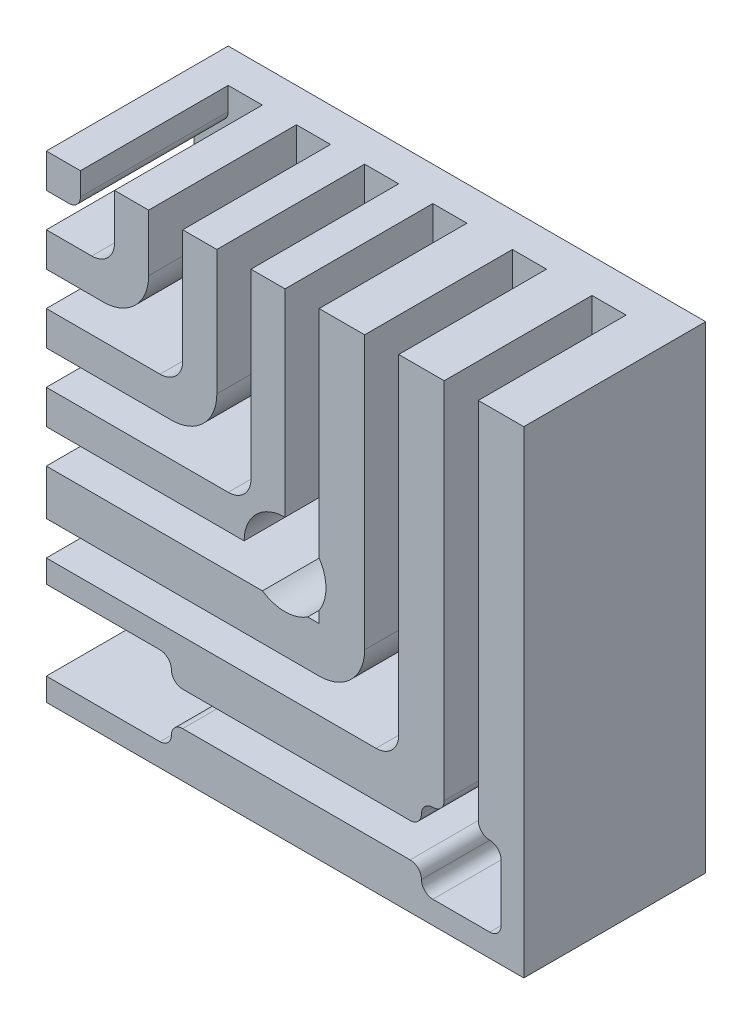
SolidWorks part; units mm, degrees
ref_plane "Front Plane" through (0, 0, 0) normal (0, 0, 1) x (1, 0, 0)
ref_plane "Top Plane" through (0, 0, 0) normal (0, 1, 0) x (1, 0, 0)
ref_plane "Right Plane" through (0, 0, 0) normal (1, 0, 0) x (0, 0, -1)
sketch "Sketch1" plane through (0, 0, 0) normal (0, 0, 1) x (1, 0, 0)
  line L1 (0, 0) -> (42, 0)
  line L2 (0, 0) -> (0, 42)
  line L3 (0, 42) -> (42, 42)
  line L4 (42, 0) -> (42, 42)
  dimension "D1" = 42
  dimension "D2" = 42
extrude "Boss-Extrude1" add sketch "Sketch1" along normal blind 16
sketch "Sketch2" plane through (0, 0, 16) normal (0, 0, 1) x (1, 0, 0)
  line L20 (3, 42) -> (3, 39)
  line L21 (42, 42) -> (0, 42) construction
  line L22 (3, 39) -> (0, 39)
  line L23 (0, 42) -> (0, 0) construction
  line L24 (0, 39) -> (0, 36)
  line L25 (0, 36) -> (6, 36)
  line L26 (6, 36) -> (6, 42)
  line L27 (6, 42) -> (3, 42)
  line L28 (9, 42) -> (9, 33)
  line L29 (9, 33) -> (0, 33)
  line L30 (0, 33) -> (0, 30)
  line L31 (0, 30) -> (12, 30)
  line L32 (12, 30) -> (12, 42)
  line L33 (12, 42) -> (9, 42)
  line L34 (15, 42) -> (15, 27)
  line L35 (15, 27) -> (0, 27)
  line L36 (0, 27) -> (0, 24)
  line L37 (0, 24) -> (18, 24)
  line L38 (18, 24) -> (18, 42)
  line L39 (18, 42) -> (15, 42)
  line L40 (0, 21) -> (21, 21)
  line L41 (21, 21) -> (21, 42)
  line L42 (21, 42) -> (24, 42)
  line L43 (24, 42) -> (24, 18)
  line L44 (24, 18) -> (0, 18)
  line L45 (0, 18) -> (0, 21)
  line L46 (28, 42) -> (28, 14)
  line L47 (28, 14) -> (0, 14)
  line L48 (0, 14) -> (0, 11)
  line L49 (0, 11) -> (31, 11)
  line L50 (31, 11) -> (31, 42)
  line L51 (31, 42) -> (28, 42)
  line L52 (35, 42) -> (35, 7)
  line L53 (35, 7) -> (0, 7)
  line L54 (0, 7) -> (0, 4)
  line L55 (0, 4) -> (38, 4)
  line L56 (38, 4) -> (38, 42)
  line L57 (38, 42) -> (35, 42)
  dimension "D1" = 3
  dimension "D2" = 3
  dimension "D3" = 3
  dimension "D4" = 3
  dimension "D5" = 3
  dimension "D6" = 3
  dimension "D7" = 3
  dimension "D8" = 3
  dimension "D9" = 4
  dimension "D10" = 3
  dimension "D11" = 4
  dimension "D12" = 3
  dimension "D13" = 3
  dimension "D14" = 3
  dimension "D15" = 3
  dimension "D16" = 3
  dimension "D17" = 3
  dimension "D18" = 3
  dimension "D19" = 3
  dimension "D20" = 3
  dimension "D21" = 4
  dimension "D22" = 3
  dimension "D23" = 4
  dimension "D24" = 3
extrude "Cut-Extrude1" cut sketch "Sketch2" against normal blind 13
sketch "Sketch3" plane through (0, 0, 0) normal (0, 0, -1) x (-1, 0, 0)
  line L0 (-21, 42) -> (-21, 0) construction
  line L1 (-42, 42) -> (0, 42) construction
  line L2 (0, 0) -> (-42, 0) construction
  line L3 (-42, 21) -> (0, 21) construction
  line L4 (-42, 0) -> (-42, 42) construction
  line L5 (0, 42) -> (0, 0) construction
  line L6 (0, 5.5) -> (-42, 5.5) construction
  line L7 (-36.5, 42) -> (-36.5, 0) construction
  line L8 (-5.5, 42) -> (-5.5, 0) construction
  circle A0 centre (-21, 21) radius 3.6
  circle A1 centre (-5.5, 5.5) radius 1.6
  circle A2 centre (-36.5, 5.5) radius 1.6
  point P24 (-36.5, 5.5)
  dimension "D4" = 7.2
  dimension "D5" = 3.2
  dimension "D1" = 5.5
  dimension "D2" = 5.5
  dimension "D3" = 5.5
extrude "Cut-Extrude2" cut sketch "Sketch3" against normal through all
sketch "Sketch4" plane through (0, 0, 3) normal (0, 0, 1) x (1, 0, 0)
  line L0 (0, 11) -> (0, 7) construction
  line L1 (11, 2) -> (0, 2)
  line L2 (11, 2) -> (11, 9)
  line L3 (11, 9) -> (0, 9)
  line L4 (0, 2) -> (0, 9)
  line L5 (11, 2) -> (0, 9) construction
  line L6 (11, 9) -> (0, 2) construction
  line L8 (33, 9) -> (40, 9)
  line L9 (33, 9) -> (33, 2)
  line L10 (33, 2) -> (40, 2)
  line L11 (40, 9) -> (40, 2)
  line L12 (33, 9) -> (40, 2) construction
  line L13 (33, 2) -> (40, 9) construction
  point P0 (5.5, 5.5)
  point P8 (36.5, 5.5)
  dimension "D1" = 7
  dimension "D2" = 7
  dimension "D3" = 7
extrude "Cut-Extrude3" cut sketch "Sketch4" along normal through all
fillet "Fillet2" radius 1 1 edges at (3, 39, 9.5)
fillet "Fillet3" radius 4 1 edges at (9, 33, 9.5)
fillet "Fillet4" radius 4 1 edges at (15, 27, 9.5)
fillet "Fillet5" radius 4 1 edges at (28, 14, 9.5)
fillet "Fillet6" radius 1 1 edges at (35, 9, 9.5)
fillet "Fillet7" radius 1 1 edges at (33, 7, 9.5)
fillet "Fillet8" radius 1 1 edges at (40, 2, 9.5)
fillet "Fillet10" radius 1 5 edges at (33, 9, 9.5) (33, 8.5, 3) (33, 8.5, 16) (33.5, 9, 16) (33.5, 9, 3)
fillet "Fillet11" radius 1 1 edges at (38, 9, 9.5)
fillet "Fillet12" radius 1 3 edges at (40, 9, 9.5) (39.5, 9, 3) (39.5, 9, 16)
fillet "Fillet13" radius 1 1 edges at (33, 2, 9.5)
fillet "Fillet14" radius 1 3 edges at (33, 3.5, 3) (33, 3.5, 16) (33, 4, 9.5)
fillet "Fillet15" radius 1 1 edges at (11, 4, 9.5)
fillet "Fillet16" radius 1 3 edges at (11, 2, 9.5) (11, 2.5, 3) (11, 2.5, 16)
fillet "Fillet17" radius 1 1 edges at (11, 7, 9.5)
fillet "Fillet18" radius 1 3 edges at (11, 9, 9.5) (11, 8.5, 16) (11, 8.5, 3)
fillet "Fillet19" radius 2 1 edges at (6, 36, 9.5)
fillet "Fillet20" radius 2 1 edges at (12, 30, 9.5)
fillet "Fillet21" radius 2 1 edges at (18, 24, 9.5)
fillet "Fillet22" radius 2 1 edges at (31, 11, 9.5)
